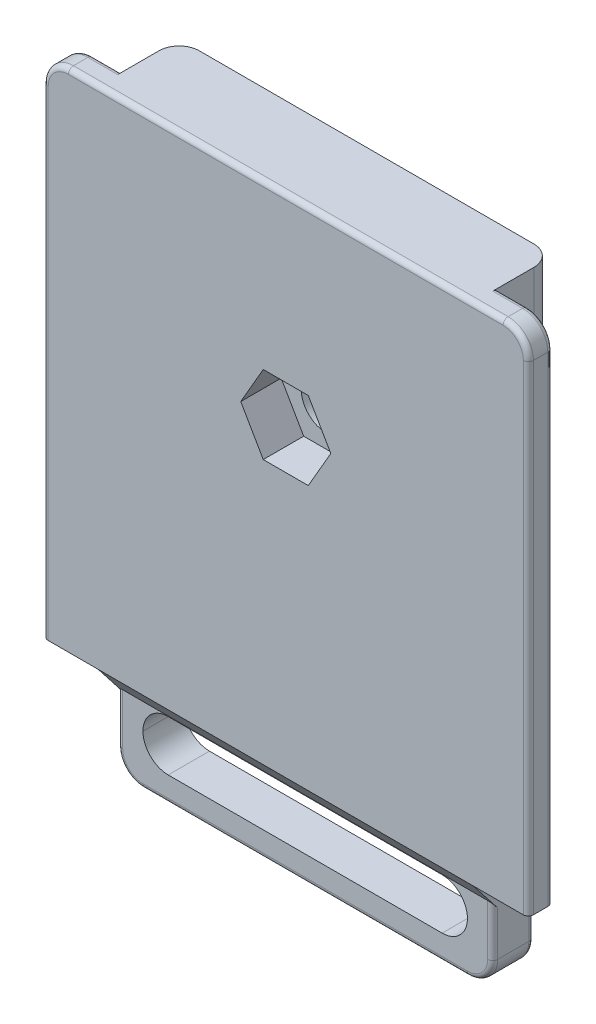
SolidWorks part; units mm, degrees
material "ABS"
ref_plane "Front Plane" through (0, 0, 0) normal (0, 0, 1) x (1, 0, 0)
ref_plane "Top Plane" through (0, 0, 0) normal (0, 1, 0) x (1, 0, 0)
ref_plane "Right Plane" through (0, 0, 0) normal (1, 0, 0) x (0, 0, -1)
sketch "Sketch1" plane through (0, 0, 0) normal (0, 1, 0) x (1, 0, 0)
  line L0 (-30.48, 0) -> (-30.48, 3.0734)
  line L1 (-30.48, 3.0734) -> (-23.5585, 3.0734)
  line L2 (-23.5585, 3.0734) -> (-23.5585, 10.16)
  line L3 (0, 0) -> (0, 10.16) construction
  line L4 (-30.48, 0) -> (30.48, 0)
  line L5 (-23.5585, 10.16) -> (23.5585, 10.16)
  line L6 (23.5585, 3.0734) -> (23.5585, 10.16)
  line L7 (30.48, 3.0734) -> (23.5585, 3.0734)
  line L8 (30.48, 0) -> (30.48, 3.0734)
  dimension "D1" = 10.16
  dimension "D2" = 3.0734
  dimension "D3" = 60.96
  dimension "D4" = 47.117
extrude "Boss-Extrude1" add sketch "Sketch1" along normal blind 63.5
sketch "Sketch2" plane through (0, 0, 0) normal (0, 0, 1) x (1, 0, 0)
  line L0 (0, 63.5) -> (0, 0) construction
  line L1 (-30.48, 63.5) -> (30.48, 63.5) construction
  circle A0 centre (0, 38.1) radius 3.125
  dimension "D1" = 6.25
  dimension "D2" = 25.4
extrude "Cut-Extrude1" cut sketch "Sketch2" against normal through all
sketch "Sketch3" plane through (0, 0, 0) normal (0, 0, 1) x (1, 0, 0)
  line L1 (5.658, 38.1) -> (2.829, 43)
  line L2 (2.829, 43) -> (-2.829, 43)
  line L3 (-2.829, 43) -> (-5.658, 38.1)
  line L4 (-5.658, 38.1) -> (-2.829, 33.2)
  line L5 (-2.829, 33.2) -> (2.829, 33.2)
  line L6 (2.829, 33.2) -> (5.658, 38.1)
  circle A0 centre (0, 38.1) radius 4.9 construction
  dimension "D1" = 9.8
extrude "Cut-Extrude2" cut sketch "Sketch3" against normal blind 5.08
fillet "Fillet1" radius 2.54 2 edges at (23.5585, 31.75, -10.16) (-23.5585, 31.75, -10.16)
fillet "Fillet2" radius 0.635 2 edges at (30.48, 31.75, -3.0734) (-30.48, 31.75, -3.0734)
sketch "Sketch4" plane through (0, 0, 0) normal (0, -1, 0) x (1, 0, 0)
  line L0 (-23.5585, -3.0734) -> (-29.845, -3.0734) construction
  line L1 (-23.5585, -2.4384) -> (23.5585, -2.4384)
  line L2 (-23.5585, -2.4384) -> (-23.5585, -7.62)
  line L3 (-23.5585, -7.62) -> (23.5585, -7.62)
  line L4 (23.5585, -2.4384) -> (23.5585, -7.62)
  line L5 (-23.5585, -2.4384) -> (23.5585, -7.62) construction
  line L6 (-23.5585, -7.62) -> (23.5585, -2.4384) construction
  point P4 (0, -5.0292)
  dimension "D1" = 0.635
  dimension "D2" = 47.117
extrude "Boss-Extrude2" add sketch "Sketch4" along normal blind 12.7
sketch "Sketch5" plane through (0, 0, -7.62) normal (0, 0, -1) x (-1, 0, 0)
  line L0 (0, 0) -> (0, -12.7) construction
  line L1 (-20.3835, -3.175) -> (20.3835, -3.175)
  line L2 (-20.3835, -3.175) -> (-20.3835, -9.525)
  line L3 (-20.3835, -9.525) -> (20.3835, -9.525)
  line L4 (20.3835, -3.175) -> (20.3835, -9.525)
  line L5 (-20.3835, -3.175) -> (20.3835, -9.525) construction
  line L6 (-20.3835, -9.525) -> (20.3835, -3.175) construction
  line L7 (23.5585, -12.7) -> (-23.5585, -12.7) construction
  line L8 (-23.5585, -12.7) -> (-23.5585, 0) construction
  point P0 (0, -6.35)
  point P11 (0, -6.35)
  dimension "D1" = 3.175
  dimension "D2" = 3.175
extrude "Cut-Extrude3" cut sketch "Sketch5" against normal through all
chamfer "Chamfer1" distance 2.4384 angle 52 2 edges at (0, 0, -2.4384) (0, 0, -7.62) first distance on face at (0, 0, -2.231) first distance on face at (0, 0, -9.153)
fillet "Fillet3" radius 3.175 6 edges at (23.5585, -12.7, -5.0292) (-23.5585, -12.7, -5.0292) (20.3835, -9.525, -5.0292) (20.3835, -3.175, -5.0292) (-20.3835, -9.525, -5.0292) (-20.3835, -3.175, -5.0292)
fillet "Fillet4" radius 0.635 19 edges at (23.5585, -6.323, -2.4384) (22.6286, -11.7701, -2.4384) (-23.5585, -6.323, -2.4384) (-22.6286, -11.7701, -2.4384) (-23.5585, -6.323, -7.62) (-22.6286, -11.7701, -7.62) (23.5585, -6.323, -7.62) (22.6286, -11.7701, -7.62) (0, -12.7, -2.4384) (0, -12.7, -7.62) (0, 63.5, 0) (30.48, 31.75, 0) (-30.48, 31.75, 0) (-30.48, 63.5, -1.2192) (-30.294, 63.5, -2.8874) (30.48, 63.5, -1.2192) (30.294, 63.5, -2.8874) (-26.7017, 63.5, -3.0734) (26.7017, 63.5, -3.0734)
sketch "Sketch7" plane through (0, 0, -3.0734) normal (0, 0, -1) x (-1, 0, 0)
  line L1 (-30.48, 63.5) -> (-27.305, 63.5)
  line L2 (-29.845, 63.5) -> (-23.5585, 63.5) construction
  line L3 (-30.48, 0) -> (-30.48, 62.865) construction
  line L4 (-30.48, 60.325) -> (-30.48, 63.5)
  line L5 (0, 38.1) -> (0, 71.2648) construction
  line L6 (30.48, 60.325) -> (30.48, 63.5)
  line L7 (30.48, 63.5) -> (27.305, 63.5)
  arc A0 (-27.305, 63.5) -> (-30.48, 60.325) centre (-27.305, 60.325) ccw
  arc A1 (27.305, 63.5) -> (30.48, 60.325) centre (27.305, 60.325) cw
  dimension "D1" = 3.175
extrude "Cut-Extrude4" cut sketch "Sketch7" against normal through all
fillet "Fillet5" radius 0.635 4 edges at (-29.5501, 62.5701, -3.0734) (-29.5501, 62.5701, 0) (29.5501, 62.5701, 0) (29.5501, 62.5701, -3.0734)
